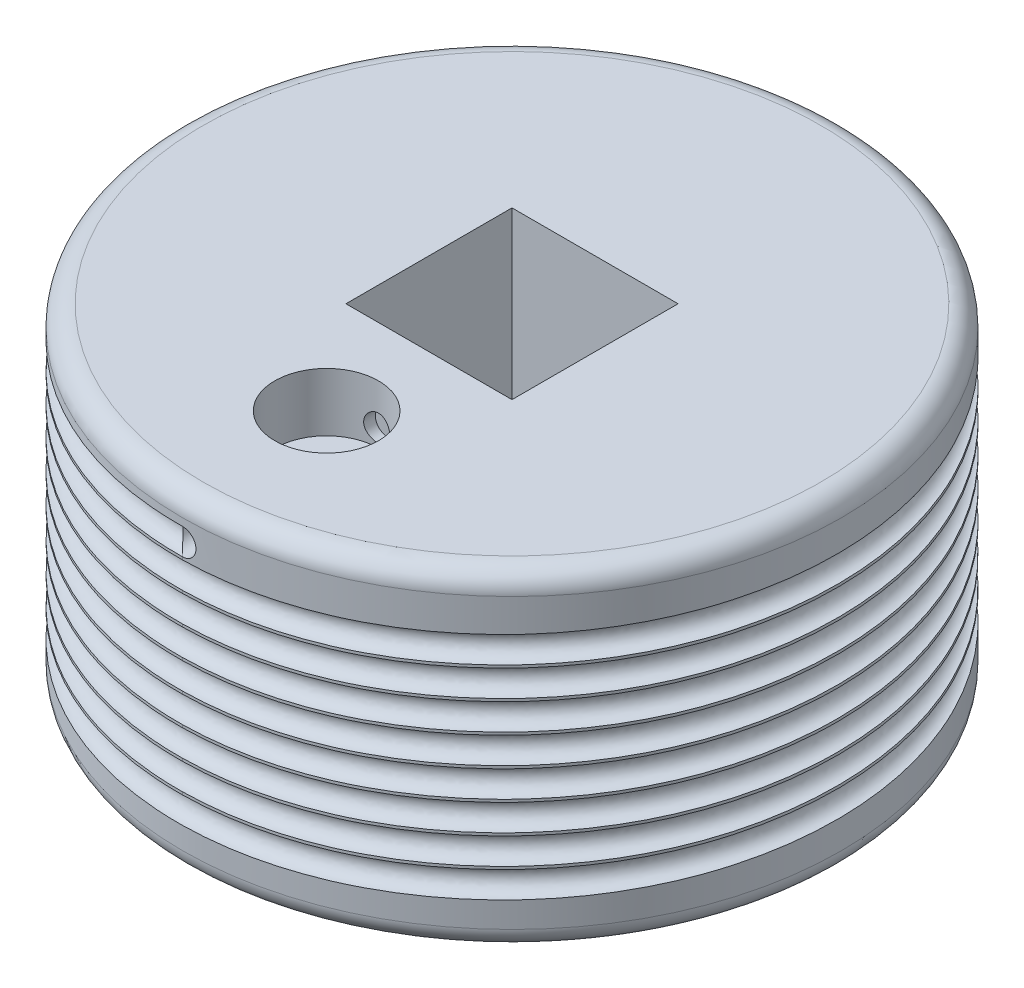
SolidWorks part; units mm, degrees
ref_plane "Front Plane" through (0, 0, 0) normal (0, 0, 1) x (1, 0, 0)
ref_plane "Top Plane" through (0, 0, 0) normal (0, 1, 0) x (1, 0, 0)
ref_plane "Right Plane" through (0, 0, 0) normal (1, 0, 0) x (0, 0, -1)
sketch "Sketch1" plane through (0, 0, 0) normal (0, 1, 0) x (1, 0, 0)
  line L1 (-3.2004, 3.2004) -> (3.2004, 3.2004)
  line L2 (-3.2004, 3.2004) -> (-3.2004, -3.2004)
  line L3 (-3.2004, -3.2004) -> (3.2004, -3.2004)
  line L4 (3.2004, 3.2004) -> (3.2004, -3.2004)
  line L5 (-3.2004, 3.2004) -> (3.2004, -3.2004) construction
  line L6 (-3.2004, -3.2004) -> (3.2004, 3.2004) construction
  circle A0 centre (0, 0) radius 12.7
  dimension "D1" = 25.4
  dimension "D2" = 6.4008
extrude "Boss-Extrude1" add sketch "Sketch1" along normal blind 12.7
ref_plane "Plane1" through (0, 1.5875, 0) normal (0, -1, 0) x (-1, 0, 0)
sketch "Sketch2" plane through (0, 1.5875, 0) normal (0, -1, 0) x (-1, 0, 0)
  circle A0 centre (0, 0) radius 12.7 construction
  circle A1 centre (0, 0) radius 12.7
curve "Helix/Spiral1" pitch 1.1206 height 9.525 radius 12.7 centre (0, 1.5875, 0) axis (0, 1, 0) start towards (0, 0, -1)
sweep "Cut-Sweep1" cut path "Helix/Spiral1" align with end faces yes circular profile diameter 1.016 parameters "D3"=1.016
ref_plane "Plane2" through (0, 0, 12.7) normal (0, 0, 1) x (1, 0, 0)
sketch "Sketch22" plane through (0, 0, 12.7) normal (0, 0, 1) x (1, 0, 0)
  line L0 (-0.0071, 11.6204) -> (0.0071, 10.6046) construction
  circle A0 centre (0, 11.1125) radius 0.508
extrude "Cut-Extrude1" cut sketch "Sketch22" against normal blind 7.9375
sketch "Sketch23" plane through (0, 12.7, 0) normal (0, 1, 0) x (1, 0, 0)
  circle A0 centre (0, -7.1437) radius 1
  point P2 (0, 0)
  dimension "D2" = 2
  dimension "D1" = 7.1437
extrude "Cut-Extrude2" cut sketch "Sketch23" against normal blind 9.525
sketch "Sketch24" plane through (0, 12.7, 0) normal (0, 1, 0) x (1, 0, 0)
  circle A0 centre (0, -7.1437) radius 2
  dimension "D1" = 4
extrude "Cut-Extrude3" cut sketch "Sketch24" against normal blind 2.25
ref_plane "Plane3" through (0, 0, -12.7) normal (0, 0, -1) x (-1, 0, 0)
sketch "Sketch25" plane through (0, 0, -12.7) normal (0, 0, -1) x (-1, 0, 0)
  line L0 (0.0071, 1.0796) -> (-0.0071, 2.0954) construction
  circle A0 centre (0, 1.5875) radius 0.508
extrude "Cut-Extrude4" cut sketch "Sketch25" against normal blind 7.9375
sketch "Sketch29" plane through (0, 0, 0) normal (0, -1, 0) x (1, 0, 0)
  circle A0 centre (0, -7.1437) radius 1
  circle A1 centre (0, 7.1437) radius 1 construction
  point P2 (0, 0)
  dimension "D1" = 7.1437
extrude "Cut-Extrude5" cut sketch "Sketch29" against normal blind 9.525
sketch "Sketch30" plane through (0, 0, 0) normal (0, -1, 0) x (1, 0, 0)
  circle A0 centre (0, -7.1437) radius 2
  dimension "D1" = 4
extrude "Cut-Extrude6" cut sketch "Sketch30" against normal blind 2.25
fillet "Fillet1" radius 0.7937 2 edges at (0, 0, 12.7) (0, 12.7, 12.7)
